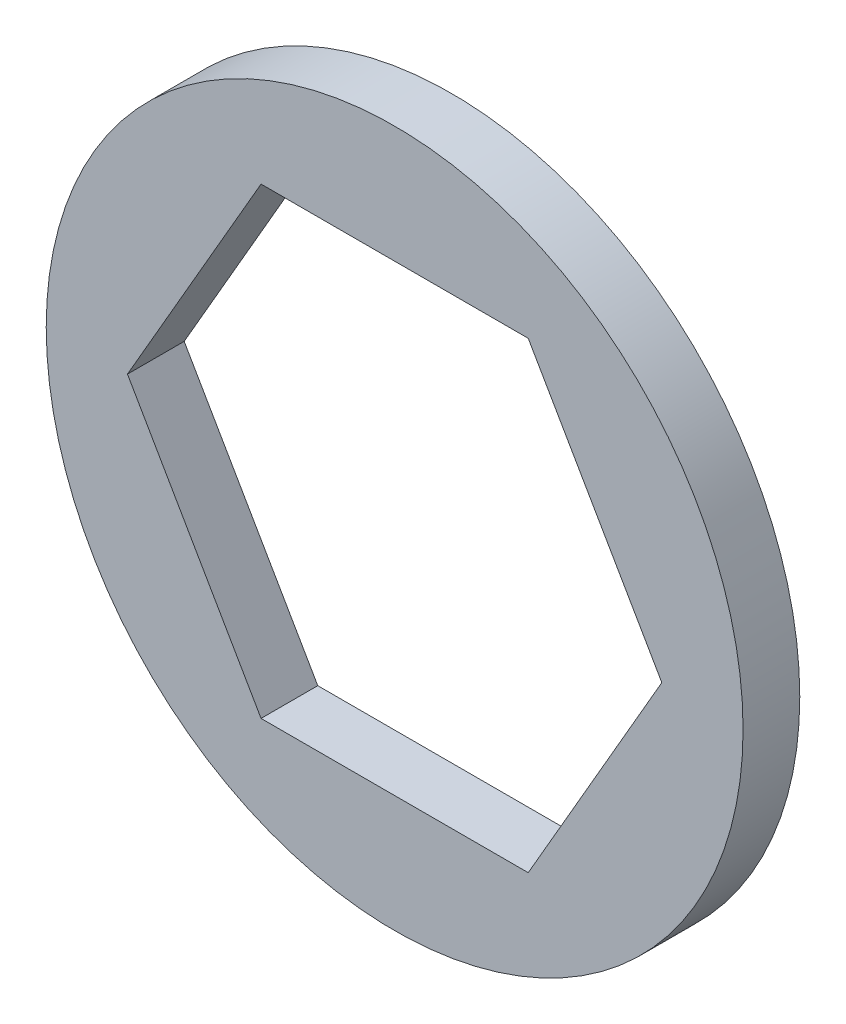
SolidWorks part; units mm, degrees
ref_plane "Front Plane" through (0, 0, 0) normal (0, 0, 1) x (1, 0, 0)
ref_plane "Top Plane" through (0, 0, 0) normal (0, 1, 0) x (1, 0, 0)
ref_plane "Right Plane" through (0, 0, 0) normal (1, 0, 0) x (0, 0, -1)
sketch "Sketch1" plane through (0, 0, 0) normal (0, 0, 1) x (1, 0, 0)
  line L1 (7.479, 0) -> (3.7395, 6.477)
  line L2 (3.7395, 6.477) -> (-3.7395, 6.477)
  line L3 (-3.7395, 6.477) -> (-7.479, 0)
  line L4 (-7.479, 0) -> (-3.7395, -6.477)
  line L5 (-3.7395, -6.477) -> (3.7395, -6.477)
  line L6 (3.7395, -6.477) -> (7.479, 0)
  circle A0 centre (0, 0) radius 6.477 construction
  circle A1 centre (0, 0) radius 9.7536
extrude "Boss-Extrude1" add sketch "Sketch1" along normal blind 1.5875
ref_axis "Center_Axis" through (0, 0, 15.0955) along (0, 0, -1)
